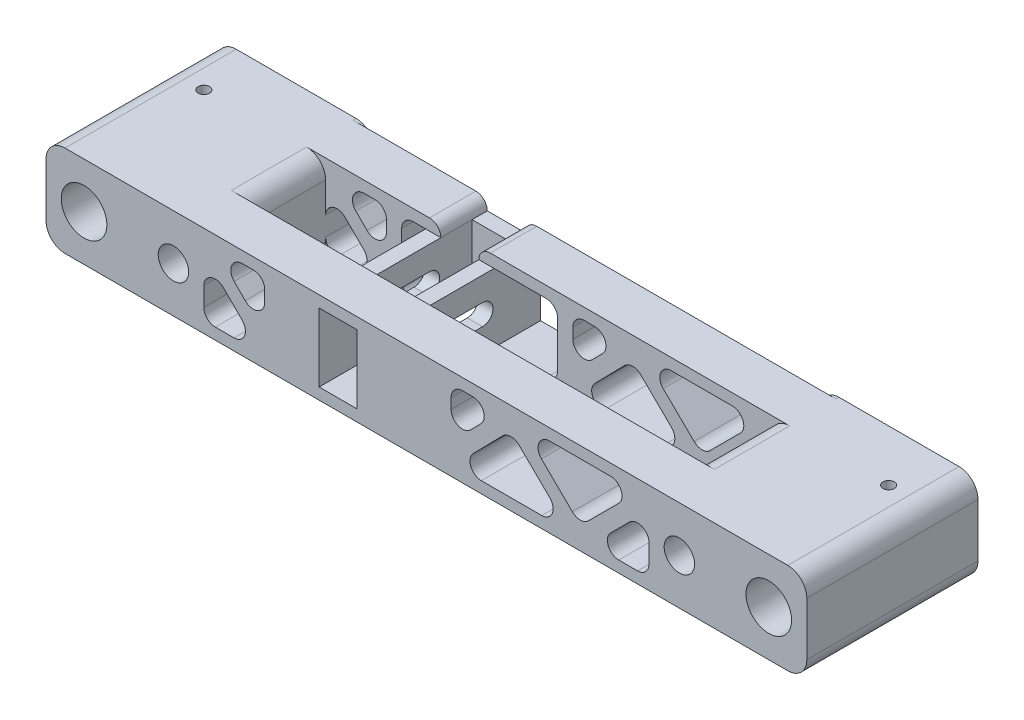
SolidWorks part; units mm, degrees
ref_plane "Front Plane" through (0, 0, 0) normal (0, 0, 1) x (1, 0, 0)
ref_plane "Top Plane" through (0, 0, 0) normal (0, 1, 0) x (1, 0, 0)
ref_plane "Right Plane" through (0, 0, 0) normal (1, 0, 0) x (0, 0, -1)
sketch "Sketch1" plane through (0, 0, 0) normal (0, 0, 1) x (1, 0, 0)
  line L0 (-58.5, 24) -> (-58.5, 0) construction
  line L1 (0, 0) -> (-100, 0)
  line L2 (0, 0) -> (0, 24)
  line L3 (0, 24) -> (-100, 24)
  line L4 (-100, 0) -> (-100, 24)
  circle A0 centre (-90, 12) radius 6
  circle A1 centre (-66.5, 12) radius 4
  point P9 (-100, 12)
  dimension "D3" = 12
  dimension "D4" = 8
  dimension "D1" = 100
  dimension "D2" = 24
  dimension "D5" = 23.5
  dimension "D6" = 10
  dimension "D7" = 8
  dimension "D8" = 41.5
extrude "Boss-Extrude1" add sketch "Sketch1" along normal blind 40
sketch "Sketch2" plane through (0, 0, 0) normal (0, 0, -1) x (-1, 0, 0)
  line L1 (100, 24) -> (0, 24)
  line L2 (100, 24) -> (100, 0)
  line L3 (100, 0) -> (0, 0)
  line L4 (0, 24) -> (0, 0)
extrude "Boss-Extrude2" add sketch "Sketch2" along normal blind 5
sketch "Sketch3" plane through (0, 24, 0) normal (0, 1, 0) x (1, 0, 0)
  line L0 (0, -40) -> (0, 5) construction
  line L1 (0, 5) -> (-58.5, 5)
  line L2 (0, 5) -> (0, -27.8)
  line L3 (0, -27.8) -> (-58.5, -27.8)
  line L4 (-58.5, 5) -> (-58.5, -27.8)
  line L5 (-100, -40) -> (-100, 5) construction
  line L7 (0, -40) -> (-100, -40) construction
  line L8 (-100, 5) -> (0, 5) construction
  dimension "D1" = 41.5
  dimension "D3" = 12.2
extrude "Cut-Extrude1" cut sketch "Sketch3" against normal up to next
mirror "Mirror2" of "Boss-Extrude2", "Cut-Extrude1", "Boss-Extrude1"
sketch "Sketch4" plane through (0, 0, 27.8) normal (0, 0, -1) x (-1, 0, 0)
  line L0 (58.5, 0) -> (58.5, 24) construction
  line L1 (28.2, 3) -> (18.2, 3)
  line L2 (28.2, 3) -> (28.2, 21)
  line L3 (28.2, 21) -> (18.2, 21)
  line L4 (18.2, 3) -> (18.2, 21)
  line L5 (28.2, 3) -> (18.2, 21) construction
  line L6 (28.2, 21) -> (18.2, 3) construction
  point P0 (23.2, 12)
  point P7 (58.5, 12)
  dimension "D1" = 30.3
  dimension "D2" = 10
  dimension "D3" = 18
extrude "Cut-Extrude2" cut sketch "Sketch4" against normal through all
sketch "Sketch5" plane through (0, 0, 27.8) normal (0, 0, -1) x (-1, 0, 0)
  line L0 (18.2, 3) -> (28.2, 3) construction
  line L1 (28.2, 21) -> (32.2, 21)
  line L2 (28.2, 21) -> (28.2, 3)
  line L3 (28.2, 3) -> (32.2, 3)
  line L4 (32.2, 21) -> (32.2, 3)
  line L5 (18.2, 21) -> (14.2, 21)
  line L6 (18.2, 21) -> (18.2, 3)
  line L7 (18.2, 3) -> (14.2, 3)
  line L8 (14.2, 21) -> (14.2, 3)
  dimension "D1" = 4
  dimension "D2" = 4
extrude "Boss-Extrude3" add sketch "Sketch5" along normal blind 28
sketch "Sketch6" plane through (0, 0, -0.2) normal (0, 0, -1) x (-1, 0, 0)
  line L1 (14.2, 21) -> (32.2, 21)
  line L2 (14.2, 21) -> (14.2, 3)
  line L3 (14.2, 3) -> (32.2, 3)
  line L4 (32.2, 21) -> (32.2, 3)
extrude "Boss-Extrude4" add sketch "Sketch6" along normal blind 4
sketch "Sketch7" plane through (-14.2, 0, 0) normal (1, 0, 0) x (0, 0, -1)
  line L0 (-20.05, 12) -> (-11.05, 12) construction
  line L1 (-20.05, 14.75) -> (-11.05, 14.75)
  line L2 (-20.05, 9.25) -> (-11.05, 9.25)
  line L3 (-27.8, 21) -> (-27.8, 3) construction
  line L4 (4.2, 21) -> (-27.8, 21) construction
  arc A0 (-20.05, 14.75) -> (-20.05, 9.25) centre (-20.05, 12) ccw
  arc A1 (-11.05, 9.25) -> (-11.05, 14.75) centre (-11.05, 12) ccw
  point P2 (-15.55, 12)
  point P7 (-22.8, 12)
  dimension "D1" = 9
  dimension "D2" = 5.5
  dimension "D3" = 5
  dimension "D4" = 9
extrude "Cut-Extrude3" cut sketch "Sketch7" against normal up to vertex
sketch "Sketch8" plane through (0, 21, 0) normal (0, 1, 0) x (1, 0, 0)
  line L0 (-32.2, 4.2) -> (-14.2, 4.2) construction
  line L1 (-18.2, 4.2) -> (58.5, 4.2)
  line L2 (-18.2, 4.2) -> (-18.2, -8)
  line L3 (-18.2, -8) -> (58.5, -8)
  line L4 (58.5, 4.2) -> (58.5, -8)
  line L5 (-58.5, 5) -> (-58.5, -27.8) construction
  line L6 (-28.2, 4.2) -> (-58.5, 4.2)
  line L7 (-28.2, 4.2) -> (-28.2, -8)
  line L8 (-28.2, -8) -> (-58.5, -8)
  line L9 (-58.5, 4.2) -> (-58.5, -8)
  line L10 (-28.2, 0.2) -> (-28.2, -27.8) construction
  line L11 (-18.2, 0.2) -> (-18.2, -27.8) construction
  line L12 (58.5, 5) -> (58.5, -27.8) construction
  dimension "D1" = 12.2
  dimension "D2" = 12.2
extrude "Boss-Extrude5" add sketch "Sketch8" along normal up to vertex (3 mm away)
ref_plane "Plane1" through (0, 12, 0) normal (0, 1, 0) x (1, 0, 0)
mirror "Mirror4" about plane through (0, 12, 0) normal (0, 1, 0) of "Boss-Extrude5"
sketch "Sketch9" plane through (0, 0, -4.2) normal (0, 0, -1) x (-1, 0, 0)
  line L0 (-58.5, 21) -> (-40.5, 3) construction
  line L1 (-58.5, 3) -> (14.2, 3) construction
  line L2 (-40.5, 3) -> (-22.15, 21) construction
  line L3 (-58.5, 21) -> (14.2, 21) construction
  line L4 (-22.15, 21) -> (-4.4933, 3) construction
  line L5 (-4.4933, 3) -> (-4.4933, 21) construction
  line L6 (58.5, 21) -> (40.5, 3) construction
  line L7 (32.2, 3) -> (58.5, 3) construction
  line L8 (40.5, 3) -> (40.5, 21) construction
  line L9 (32.2, 21) -> (58.5, 21) construction
  line L10 (-58.5, 0) -> (-58.5, 24) construction
  line L11 (58.5, 0) -> (58.5, 24) construction
  line L12 (-58.5, 18.1716) -> (-43.3284, 3)
  line L13 (-37.6439, 3) -> (-22.1772, 18.1717)
  line L14 (-22.1772, 18.1717) -> (-7.2949, 3)
  line L15 (-2.4933, 3) -> (-2.4933, 21)
  line L16 (55.6716, 21) -> (42.5, 7.8284)
  line L17 (42.5, 7.8284) -> (42.5, 21)
  line L18 (-55.6716, 21) -> (-40.4864, 5.8149)
  line L19 (-40.4864, 5.8149) -> (-25.0061, 21)
  line L20 (-19.3484, 21) -> (-6.4933, 7.8949)
  line L21 (-6.4933, 7.8949) -> (-6.4933, 21)
  line L22 (58.5, 18.1716) -> (43.3284, 3)
  line L23 (38.5, 3) -> (38.5, 21)
  line L24 (-58.5, 18.1716) -> (-58.5, 21)
  line L25 (-58.5, 21) -> (-55.6716, 21)
  line L26 (-6.4933, 21) -> (-2.4933, 21)
  line L27 (-7.2949, 3) -> (-2.4933, 3)
  line L28 (-37.6439, 3) -> (-43.3284, 3)
  line L29 (-25.0061, 21) -> (-19.3484, 21)
  line L30 (-57.0858, 22.4142) -> (-40.4864, 5.8149) construction
  line L31 (-59.9142, 19.5858) -> (-40.5136, 0.1851) construction
  line L32 (-40.5136, 0.1851) -> (-22.1772, 18.1717) construction
  line L33 (-22.1772, 18.1717) -> (-2.4933, -1.8949) construction
  line L34 (-2.4933, -1.8949) -> (-2.4933, 21) construction
  line L35 (-22.1228, 23.8283) -> (-6.4933, 7.8949) construction
  line L36 (-40.4864, 5.8149) -> (-22.1228, 23.8283) construction
  line L37 (38.5, 21) -> (42.5, 21)
  line L38 (55.6716, 21) -> (58.5, 21)
  line L39 (58.5, 21) -> (58.5, 18.1716)
  line L40 (58.5, 0) -> (58.5, 24) construction
  line L41 (43.3284, 3) -> (38.5, 3)
  line L42 (38.5, -1.8284) -> (38.5, 21) construction
  line L43 (59.9142, 19.5858) -> (38.5, -1.8284) construction
  line L44 (57.0858, 22.4142) -> (42.5, 7.8284) construction
  dimension "D1" = 45
  dimension "D2" = 45
  dimension "D3" = 2
  dimension "D4" = 2
extrude "Boss-Extrude6" add sketch "Sketch9" against normal up to vertex (12.2 mm away) up to point (-14.2, 21, 8)
fillet "Fillet1" radius 5 10 edges at (-100, 0, 17.5) (-100, 24, 17.5) (100, 0, 17.5) (100, 24, 17.5) (58.5, 0, 17.9) (58.5, 24, 17.9) (-58.5, 24, -4.6) (-58.5, 0, 17.9) (-58.5, 24, 17.9) (58.5, 24, -4.6)
fillet "Fillet2" radius 3 38 edges at (-30.2, 3, 27.8) (-30.2, 21, 27.8) (-16.2, 21, 27.8) (-16.2, 3, 27.8) (-18.2, 22.5, -4.2) (-18.2, 22.5, 8) (-18.2, 24, 1.9) (-28.2, 22.5, 8) (-28.2, 22.5, -4.2) (-28.2, 24, 1.9) (-18.2, 0, 1.9) (-18.2, 1.5, 8) (-18.2, 1.5, -4.2) (-28.2, 0, 1.9) (-28.2, 1.5, -4.2) (-28.2, 1.5, 8) (55.6716, 21, 1.9) (40.4864, 5.8149, 1.9) (25.0061, 21, 1.9) (19.3484, 21, 1.9) (6.4933, 7.8949, 1.9) (6.4933, 21, 1.9) (2.4933, 21, 1.9) (2.4933, 3, 1.9) (7.2949, 3, 1.9) (22.1772, 18.1717, 1.9) (37.6439, 3, 1.9) (43.3284, 3, 1.9) (58.5, 18.1716, 1.9) (-58.5, 18.1716, 1.9) (-43.3284, 3, 1.9) (-38.5, 3, 1.9) (-38.5, 21, 1.9) (-42.5, 21, 1.9) (-42.5, 7.8284, 1.9) (-55.6716, 21, 1.9) (58.9174, 3, 1.9) (-58.9174, 3, 1.9)
sketch "Sketch10" plane through (0, 0, 40) normal (0, 0, 1) x (1, 0, 0)
  line L0 (42.5874, 7.9159) -> (50.5503, 15.8787) construction
  line L1 (30.2477, 15.8584) -> (38.3653, 7.8955) construction
  line L2 (32.3485, 21) -> (48.4289, 21) construction
  line L3 (53.3787, 13.0503) -> (48.4497, 8.1213) construction
  line L4 (50.5711, 3) -> (55.5, 3) construction
  line L5 (32.4023, 8.1416) -> (24.3189, 16.0709) construction
  line L6 (20.0764, 16.0301) -> (12.2984, 8.1008) construction
  line L7 (14.4401, 3) -> (30.3015, 3) construction
  line L8 (11.635, 13.1366) -> (14.3449, 15.8992) construction
  line L9 (9.4933, 21) -> (12.2033, 21) construction
  line L10 (6.4933, 18) -> (6.4933, 15.2374) construction
  line L11 (-48.4289, 21) -> (-45.5, 21) construction
  line L12 (-42.5, 15.0711) -> (-42.5, 18) construction
  line L13 (-50.5503, 15.8787) -> (-47.6213, 12.9497) construction
  line L14 (-55.5, 3) -> (-50.5711, 3) construction
  line L15 (-55.5, 3) -> (-50.5711, 3)
  line L16 (-50.5503, 15.8787) -> (-47.6213, 12.9497)
  line L17 (-42.5, 15.0711) -> (-42.5, 18)
  line L18 (-48.4289, 21) -> (-45.5, 21)
  line L19 (6.4933, 18) -> (6.4933, 15.2374)
  line L20 (9.4933, 21) -> (12.2033, 21)
  line L21 (11.635, 13.1366) -> (14.3449, 15.8992)
  line L22 (14.4401, 3) -> (30.3015, 3)
  line L23 (20.0764, 16.0301) -> (12.2984, 8.1008)
  line L24 (32.4023, 8.1416) -> (24.3189, 16.0709)
  line L25 (50.5711, 3) -> (55.5, 3)
  line L26 (53.3787, 13.0503) -> (48.4497, 8.1213)
  line L27 (32.3485, 21) -> (48.4289, 21)
  line L28 (30.2477, 15.8584) -> (38.3653, 7.8955)
  line L29 (42.5874, 7.9159) -> (50.5503, 15.8787)
  line L30 (-48.4497, 8.1213) -> (-53.3787, 13.0503) construction
  line L31 (-48.4497, 8.1213) -> (-53.3787, 13.0503)
  line L32 (-58.5, 10.9289) -> (-58.5, 6)
  line L33 (58.5, 10.9289) -> (58.5, 6)
  arc A0 (-50.5711, 3) -> (-48.4497, 8.1213) centre (-50.5711, 6) ccw construction
  arc A1 (38.3653, 7.8955) -> (42.5874, 7.9159) centre (40.4661, 10.0372) ccw construction
  arc A2 (32.3485, 21) -> (30.2477, 15.8584) centre (32.3485, 18) ccw construction
  arc A3 (50.5503, 15.8787) -> (48.4289, 21) centre (48.4289, 18) ccw construction
  arc A4 (58.5, 10.9289) -> (53.3787, 13.0503) centre (55.5, 10.9289) ccw construction
  arc A5 (48.4497, 8.1213) -> (50.5711, 3) centre (50.5711, 6) ccw construction
  arc A6 (55.5, 3) -> (58.5, 6) centre (55.5, 6) ccw construction
  arc A7 (24.3189, 16.0709) -> (20.0764, 16.0301) centre (22.2181, 13.9293) ccw construction
  arc A8 (12.2984, 8.1008) -> (14.4401, 3) centre (14.4401, 6) ccw construction
  arc A9 (30.3015, 3) -> (32.4023, 8.1416) centre (30.3015, 6) ccw construction
  arc A10 (14.3449, 15.8992) -> (12.2033, 21) centre (12.2033, 18) ccw construction
  arc A11 (9.4933, 21) -> (6.4933, 18) centre (9.4933, 18) ccw construction
  arc A12 (6.4933, 15.2374) -> (11.635, 13.1366) centre (9.4933, 15.2374) ccw construction
  arc A13 (-42.5, 18) -> (-45.5, 21) centre (-45.5, 18) ccw construction
  arc A14 (-48.4289, 21) -> (-50.5503, 15.8787) centre (-48.4289, 18) ccw construction
  arc A15 (-47.6213, 12.9497) -> (-42.5, 15.0711) centre (-45.5, 15.0711) ccw construction
  arc A16 (-50.5711, 3) -> (-48.4497, 8.1213) centre (-50.5711, 6) ccw
  arc A17 (-47.6213, 12.9497) -> (-42.5, 15.0711) centre (-45.5, 15.0711) ccw
  arc A18 (-48.4289, 21) -> (-50.5503, 15.8787) centre (-48.4289, 18) ccw
  arc A19 (-42.5, 18) -> (-45.5, 21) centre (-45.5, 18) ccw
  arc A20 (6.4933, 15.2374) -> (11.635, 13.1366) centre (9.4933, 15.2374) ccw
  arc A21 (9.4933, 21) -> (6.4933, 18) centre (9.4933, 18) ccw
  arc A22 (14.3449, 15.8992) -> (12.2033, 21) centre (12.2033, 18) ccw
  arc A23 (30.3015, 3) -> (32.4023, 8.1416) centre (30.3015, 6) ccw
  arc A24 (12.2984, 8.1008) -> (14.4401, 3) centre (14.4401, 6) ccw
  arc A25 (24.3189, 16.0709) -> (20.0764, 16.0301) centre (22.2181, 13.9293) ccw
  arc A26 (55.5, 3) -> (58.5, 6) centre (55.5, 6) ccw
  arc A27 (48.4497, 8.1213) -> (50.5711, 3) centre (50.5711, 6) ccw
  arc A28 (58.5, 10.9289) -> (53.3787, 13.0503) centre (55.5, 10.9289) ccw
  arc A29 (50.5503, 15.8787) -> (48.4289, 21) centre (48.4289, 18) ccw
  arc A30 (32.3485, 21) -> (30.2477, 15.8584) centre (32.3485, 18) ccw
  arc A31 (38.3653, 7.8955) -> (42.5874, 7.9159) centre (40.4661, 10.0372) ccw
  arc A32 (-58.5, 6) -> (-55.5, 3) centre (-55.5, 6) ccw construction
  arc A33 (-53.3787, 13.0503) -> (-58.5, 10.9289) centre (-55.5, 10.9289) ccw construction
  arc A34 (-58.5, 6) -> (-55.5, 3) centre (-55.5, 6) ccw
  arc A35 (-53.3787, 13.0503) -> (-58.5, 10.9289) centre (-55.5, 10.9289) ccw
extrude "Cut-Extrude4" cut sketch "Sketch10" against normal up to vertex (12.2 mm away)
sketch "Sketch11" plane through (0, 24, 0) normal (0, 1, 0) x (1, 0, 0)
  line L0 (96, 0) -> (84, 0) construction
  line L1 (-84, 0) -> (-96, 0) construction
  circle A0 centre (90, -8.5) radius 1.5
  circle A1 centre (-90, -8.5) radius 1.5
  point P12 (-90, 0)
  point P13 (90, 0)
  dimension "D3" = 3
  dimension "D4" = 3
  dimension "D1" = 8.5
  dimension "D2" = 8.5
extrude "Cut-Extrude5" cut sketch "Sketch11" against normal through all
sketch "Sketch12" plane through (0, 0, 0) normal (0, -1, 0) x (1, 0, 0)
  line L0 (95, -5) -> (95, 40) construction
  line L1 (-87.25, 6.9123) -> (-87.25, 10.0877)
  line L2 (-87.25, 10.0877) -> (-90, 11.6754)
  line L3 (-90, 11.6754) -> (-92.75, 10.0877)
  line L4 (-92.75, 10.0877) -> (-92.75, 6.9123)
  line L5 (-92.75, 6.9123) -> (-90, 5.3246)
  line L6 (-90, 5.3246) -> (-87.25, 6.9123)
  line L7 (92.75, 10.0877) -> (90, 11.6754)
  line L8 (90, 11.6754) -> (87.25, 10.0877)
  line L9 (87.25, 10.0877) -> (87.25, 6.9123)
  line L10 (87.25, 6.9123) -> (90, 5.3246)
  line L11 (90, 5.3246) -> (92.75, 6.9123)
  line L12 (92.75, 6.9123) -> (92.75, 10.0877)
  line L13 (-95, 40) -> (-95, -5) construction
  circle A0 centre (-90, 8.5) radius 2.75 construction
  circle A1 centre (90, 8.5) radius 2.75 construction
  point P22 (87.25, 8.5)
  dimension "D1" = 5.5
  dimension "D2" = 5.5
extrude "Cut-Extrude6" cut sketch "Sketch12" against normal blind 4
